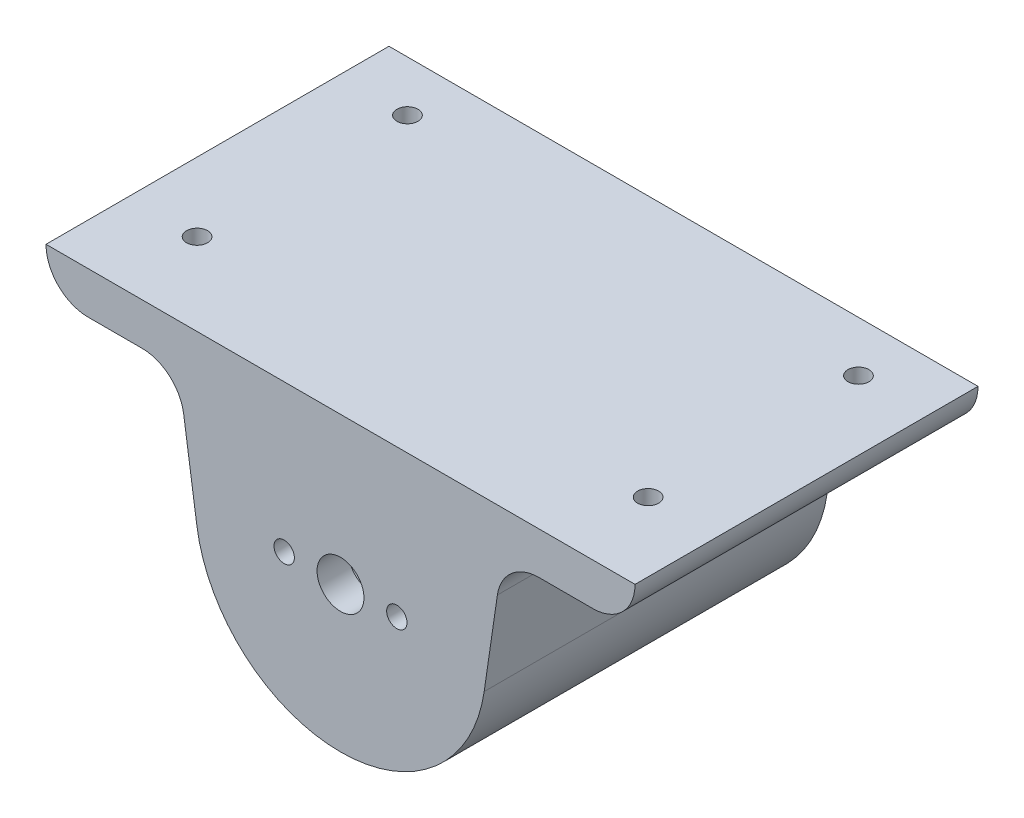
SolidWorks part; units mm, degrees
ref_plane "Front Plane" through (0, 0, 0) normal (0, 0, 1) x (1, 0, 0)
ref_plane "Top Plane" through (0, 0, 0) normal (0, 1, 0) x (1, 0, 0)
ref_plane "Right Plane" through (0, 0, 0) normal (1, 0, 0) x (0, 0, -1)
sketch "Sketch1" plane through (0, 0, 0) normal (0, 0, 1) x (1, 0, 0)
  line L0 (-25.4, 22.225) -> (25.4, 22.225)
  line L1 (-21.6803, -3.175) -> (-25.4, 22.225)
  line L2 (25.4, 22.225) -> (21.6803, -3.175)
  circle A0 centre (0, 0) radius 12.5381
  arc A1 (-21.6803, -3.175) -> (21.6803, -3.175) centre (0, 0) ccw
  point P5 (0, 22.225)
  dimension "D1" = 25.0762
  dimension "D2" = 50.8
  dimension "D3" = 22.225
  dimension "D4" = 25.4
extrude "Boss-Extrude1" add sketch "Sketch1" against normal blind 47
sketch "Sketch2" plane through (0, 22.225, 0) normal (0, 1, 0) x (1, 0, 0)
  line L0 (-25.4, 47) -> (-25.4, 0) construction
  line L1 (25.4, 47) -> (25.4, 0) construction
  line L2 (-25.4, 23.5) -> (25.4, 23.5) construction
  line L3 (25.4, 47) -> (-25.4, 47) construction
  line L4 (-44.45, 0) -> (44.45, 0)
  line L5 (-44.45, 0) -> (-44.45, 47)
  line L6 (-44.45, 47) -> (44.45, 47)
  line L7 (44.45, 0) -> (44.45, 47)
  line L8 (-44.45, 0) -> (44.45, 47) construction
  line L9 (-44.45, 47) -> (44.45, 0) construction
  point P0 (-25.4, 23.5)
  point P1 (25.4, 23.5)
  point P8 (0, 23.5)
  dimension "D1" = 88.9
extrude "Boss-Extrude2" add sketch "Sketch2" against normal blind 6.35
fillet "Fillet1" radius 6.35 4 edges at (44.45, 15.875, -23.5) (-44.45, 15.875, -23.5) (24.4701, 15.875, -23.5) (-24.4701, 15.875, -23.5)
sketch "Sketch3" plane through (0, 15.875, 0) normal (0, -1, 0) x (1, 0, 0)
  line L0 (-44.45, -23.5) -> (44.45, -23.5) construction
  line L1 (-44.45, -47) -> (-44.45, 0) construction
  line L2 (44.45, 0) -> (44.45, -47) construction
  line L3 (0, -55) -> (0, 55) construction
  circle A0 centre (-34.036, -7.625) radius 1.5875
  circle A1 centre (-34.036, -39.375) radius 1.5875
  circle A2 centre (34.036, -39.375) radius 1.5875
  circle A3 centre (34.036, -7.625) radius 1.5875
  dimension "D2" = 3.175
  dimension "D1" = 34.036
  dimension "D3" = 15.875
extrude "Cut-Extrude1" cut sketch "Sketch3" against normal blind 9.525
sketch "Sketch5" plane through (0, 0, 0) normal (0, 0, 1) x (1, 0, 0)
  line L0 (0, -24.2751) -> (0, 24.2751) construction
  line L5 (29.9579, 15.875) -> (38.1, 15.875)
  line L6 (44.45, 22.225) -> (-44.45, 22.225)
  line L7 (-38.1, 15.875) -> (-29.9579, 15.875)
  line L8 (-23.6749, 10.4451) -> (-21.6803, -3.175)
  line L9 (21.6803, -3.175) -> (23.6749, 10.4451)
  line L10 (29.9579, 15.875) -> (38.1, 15.875)
  line L11 (44.45, 22.225) -> (-44.45, 22.225)
  line L12 (-38.1, 15.875) -> (-29.9579, 15.875)
  line L13 (-23.6749, 10.4451) -> (-21.6803, -3.175)
  line L14 (21.6803, -3.175) -> (23.6749, 10.4451)
  circle A0 centre (0, 0) radius 12.5381 construction
  circle A1 centre (0, 0) radius 12.5381 construction
  circle A2 centre (0, 0) radius 3.5381
  circle A3 centre (-8.5, 0) radius 1.5381
  circle A4 centre (8.5, 0) radius 1.5381
  arc A5 (38.1, 15.875) -> (44.45, 22.225) centre (38.1, 22.225) ccw
  arc A6 (-44.45, 22.225) -> (-38.1, 15.875) centre (-38.1, 22.225) ccw
  arc A7 (-23.6749, 10.4451) -> (-29.9579, 15.875) centre (-29.9579, 9.525) ccw
  arc A8 (-21.6803, -3.175) -> (21.6803, -3.175) centre (0, 0) ccw
  arc A9 (29.9579, 15.875) -> (23.6749, 10.4451) centre (29.9579, 9.525) ccw
  arc A10 (38.1, 15.875) -> (44.45, 22.225) centre (38.1, 22.225) ccw
  arc A11 (-44.45, 22.225) -> (-38.1, 15.875) centre (-38.1, 22.225) ccw
  arc A12 (-23.6749, 10.4451) -> (-29.9579, 15.875) centre (-29.9579, 9.525) ccw
  arc A13 (-21.6803, -3.175) -> (21.6803, -3.175) centre (0, 0) ccw
  arc A14 (29.9579, 15.875) -> (23.6749, 10.4451) centre (29.9579, 9.525) ccw
  dimension "D2" = 7.0762
  dimension "D3" = 3.0762
  dimension "D4" = 8.5
  dimension "D1" = 0
extrude "Boss-Extrude3" add sketch "Sketch5" along normal blind 4.7625
